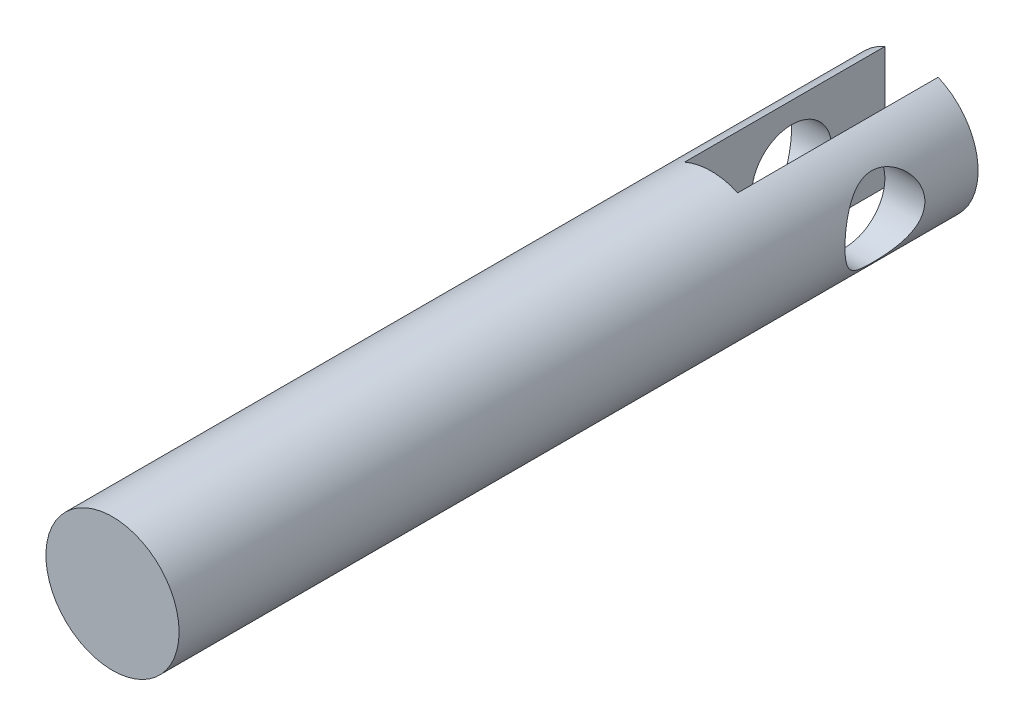
SolidWorks part; units mm, degrees
ref_plane "Front Plane" through (0, 0, 0) normal (1, 0, 0) x (0, 1, 0)
ref_plane "Top Plane" through (0, 0, 0) normal (0, 0, 1) x (0, 1, 0)
ref_plane "Right Plane" through (0, 0, 0) normal (0, 1, 0) x (-1, 0, 0)
sketch "Sketch1" plane through (0, 0, 0) normal (0, 0, 1) x (0, 1, 0)
  circle A0 centre (0, 0) radius 10
  dimension "D1" = 20
extrude "Boss-Extrude1" add sketch "Sketch1" along normal blind 120
sketch "Sketch4" plane through (0, 0, 0) normal (1, 0, 0) x (0, 1, 0)
  line L0 (-10, 14) -> (10, 14) construction
  line L1 (-10, 120) -> (-10, 0) construction
  line L2 (10, 0) -> (10, 120) construction
  line L3 (0, 0) -> (0, 20) construction
  circle A0 centre (0, 14) radius 6
  dimension "D1" = 12
extrude "Cut-Extrude3" cut sketch "Sketch4" against normal blind 40 and the other way blind 40
sketch "Sketch5" plane through (0, 0, 0) normal (1, 0, 0) x (0, 1, 0)
  line L1 (-11.1229, 30.0863) -> (12.4711, 30.0863)
  line L2 (-11.1229, 30.0863) -> (-11.1229, -3.6193)
  line L3 (-11.1229, -3.6193) -> (12.4711, -3.6193)
  line L4 (12.4711, 30.0863) -> (12.4711, -3.6193)
extrude "Cut-Extrude4" cut sketch "Sketch5" against normal blind 4 and the other way blind 4
